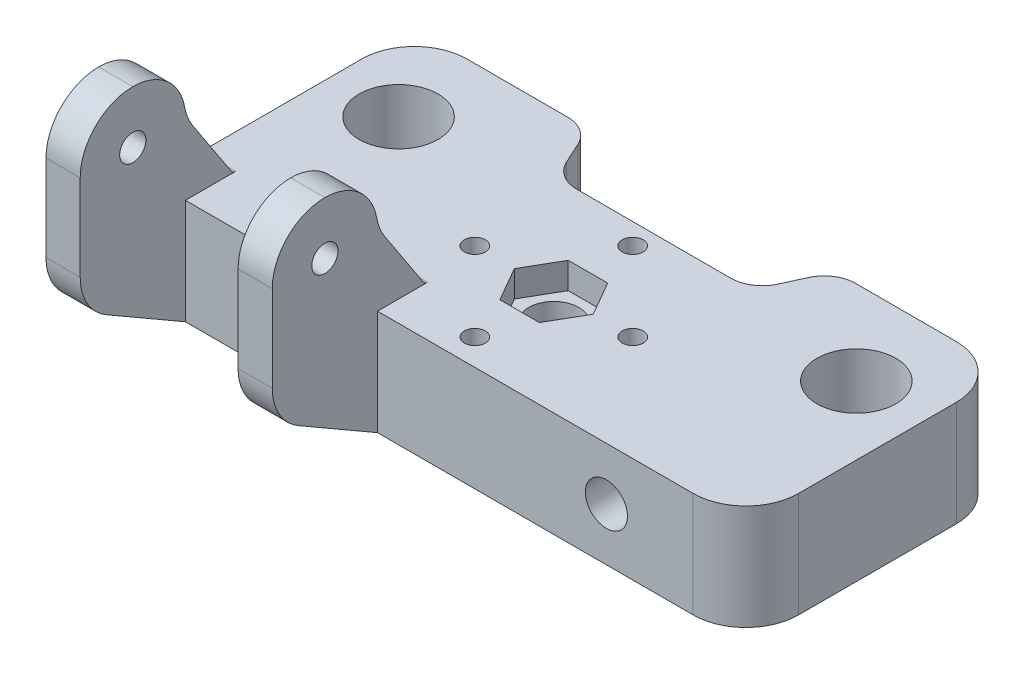
SolidWorks part; units mm, degrees
material "ABS PC"
ref_plane "Front Plane" through (0, 0, 0) normal (0, 0, 1) x (1, 0, 0)
ref_plane "Top Plane" through (0, 0, 0) normal (0, 1, 0) x (1, 0, 0)
ref_plane "Right Plane" through (0, 0, 0) normal (1, 0, 0) x (0, 0, -1)
sketch "Sketch1" plane through (0, 0, 0) normal (0, 1, 0) x (1, 0, 0)
  line L0 (56.5, 0) -> (-56.5, 0)
  line L1 (56.5, 0) -> (56.5, 50)
  line L2 (-56.5, 0) -> (-56.5, 50)
  line L3 (56.5, 50) -> (-56.5, 50)
  dimension "D1" = 113
  dimension "D2" = 50
extrude "Boss-Extrude1" add sketch "Sketch1" along normal blind 20
sketch "Sketch2" plane through (0, 20, 0) normal (0, 1, 0) x (1, 0, 0)
  line L1 (56.5, 0) -> (56.5, 50) construction
  line L3 (56.5, 50) -> (-56.5, 50) construction
  circle A0 centre (-43.5, 34) radius 7.5
  circle A1 centre (43.5, 34) radius 7.5
  circle A2 centre (0, 20) radius 4.75
  circle A3 centre (15, 20) radius 2
  circle A4 centre (-15, 20) radius 2
  circle A5 centre (0, 35) radius 2
  circle A6 centre (0, 5) radius 2
  dimension "D2" = 56.5
  dimension "D3" = 30
  dimension "D5" = 15
  dimension "D6" = 15
  dimension "D1" = 43.5
  dimension "D4" = 43.5
  dimension "D7" = 14
  dimension "D8" = 9.5
  dimension "D9" = 15
  dimension "D10" = 15
  dimension "D11" = 4
  dimension "D12" = 15
  dimension "D13" = 15
extrude "Cut-Extrude1" cut sketch "Sketch2" against normal through all
sketch "Sketch3" plane through (0, 20, 0) normal (0, 1, 0) x (1, 0, 0)
  line L1 (-3.75, 13.5048) -> (3.75, 13.5048)
  line L2 (3.75, 13.5048) -> (7.5, 20)
  line L3 (7.5, 20) -> (3.75, 26.4952)
  line L4 (3.75, 26.4952) -> (-3.75, 26.4952)
  line L5 (-3.75, 26.4952) -> (-7.5, 20)
  line L6 (-7.5, 20) -> (-3.75, 13.5048)
  circle A0 centre (0, 20) radius 6.4952 construction
  circle A1 centre (0, 20) radius 4.75 construction
  dimension "D1" = 15
extrude "Cut-Extrude2" cut sketch "Sketch3" against normal blind 5
sketch "Sketch5" plane through (0, 0, -50) normal (0, 0, -1) x (-1, 0, 0)
  line L3 (-56.5, 20) -> (-56.5, 0) construction
  line L4 (-56.5, 0) -> (56.5, 0) construction
  circle A0 centre (30, 10) radius 4
  circle A1 centre (-30, 10) radius 4
  dimension "D1" = 8
  dimension "D2" = 60
  dimension "D3" = 26.5
  dimension "D4" = 10
extrude "Cut-Extrude4" cut sketch "Sketch5" against normal through all
sketch "Sketch12" plane through (0, 20, 0) normal (0, 1, 0) x (1, 0, 0)
  line L4 (23.5, 50) -> (18.5, 39)
  line L5 (56.5, 50) -> (-56.5, 50) construction
  line L6 (18.5, 39) -> (-18.5, 39)
  line L7 (-18.5, 39) -> (-23.5, 50)
  line L8 (-23.5, 50) -> (23.5, 50)
  dimension "D2" = 11
  dimension "D3" = 33
  dimension "D4" = 33
  dimension "D5" = 5
  dimension "D6" = 5
extrude "Cut-Extrude6" cut sketch "Sketch12" against normal through all
fillet "Fillet5" radius 6 4 edges at (-23.5, 10, -50) (23.5, 10, -50) (-18.5, 10, -39) (18.5, 10, -39)
sketch "Sketch13" plane through (0, 0, 0) normal (0, 0, 1) x (1, 0, 0)
  line L0 (-50, 0) -> (-50, 43.7)
  line L1 (-50, 0) -> (-56.5, 0)
  line L2 (-50, 43.7) -> (-56.5, 43.7)
  line L3 (-56.5, 0) -> (-56.5, 43.7)
  line L4 (-56.5, 0) -> (56.5, 0) construction
  line L5 (-20, 0) -> (-13.5, 0)
  line L6 (-20, 0) -> (-20, 43.7)
  line L7 (-13.5, 0) -> (-13.5, 43.7)
  line L8 (-20, 43.7) -> (-13.5, 43.7)
  line L9 (-56.5, 20) -> (-56.5, 0) construction
  dimension "D3" = 30
  dimension "D1" = 43.7
  dimension "D2" = 6.5
extrude "Boss-Extrude2" add sketch "Sketch13" along normal blind 20
hole_wizard "Ø5.0 (5) Diameter Hole1" positions "Sketch15" profile "Sketch14" hole size "Ø5.0" standard "ANSI Metric" end condition through all
sketch "Sketch15" plane through (-13.5, 0, 0) normal (1, 0, 0) x (0, 0, -1)
  line L0 (0, 20) -> (0, 43.7) construction
  point P0 (-10, 33.7)
  dimension "D1" = 10
  dimension "D2" = 13.7
sketch "Sketch14" plane through (-13.5, 33.7, 10) normal (0, 1, 0) x (0, 0, -1)
  line L0 (0, 0) -> (0, 43)
  line L1 (0, 43) -> (2.5, 43)
  line L2 (2.5, 43) -> (2.5, 0)
  line L5 (2.5, 0) -> (0, 0)
  line L11 (0, -6.35) -> (0, 107.95) construction
  dimension "Thru Hole Dia." = 5
  dimension "Thru Hole Depth" = 43
sketch "Sketch16" plane through (-13.5, 0, 0) normal (1, 0, 0) x (0, 0, -1)
  line L0 (0, 0) -> (-20, 0)
  line L1 (-20, 0) -> (-20, 11.547)
  line L2 (-20, 0) -> (-20, 43.7) construction
  line L3 (-20, 11.547) -> (0, 0)
  dimension "D1" = 30
extrude "Cut-Extrude7" cut sketch "Sketch16" against normal through all
fillet "Fillet6" radius 10 2 edges at (-53.25, 11.547, 20) (-16.75, 11.547, 20)
fillet "Fillet7" radius 10 4 edges at (-16.75, 43.7, 0) (-16.75, 43.7, 20) (-53.25, 43.7, 20) (-53.25, 43.7, 0)
sketch "Sketch18" plane through (-56.5, 0, 0) normal (-1, 0, 0) x (0, 0, 1)
  line L0 (0, 33.7) -> (0, 20)
  line L1 (0, 20) -> (-9, 20)
  line L2 (-9, 20) -> (0, 33.7)
  dimension "D1" = 9
extrude "Boss-Extrude3" add sketch "Sketch18" against normal blind 6.5
fillet "Fillet8" radius 10 1 edges at (-53.25, 33.7, 0)
sketch "Sketch19" plane through (-13.5, 0, 0) normal (1, 0, 0) x (0, 0, -1)
  line L0 (0, 33.7) -> (0, 20)
  line L1 (0, 20) -> (9, 20)
  line L2 (9, 20) -> (0, 33.7)
  dimension "D1" = 9
extrude "Boss-Extrude4" add sketch "Sketch19" against normal blind 6.5
fillet "Fillet9" radius 10 1 edges at (-16.75, 33.7, 0)
fillet "Fillet10" radius 1 2 edges at (-16.75, 20, -9) (-53.25, 20, -9)
fillet "Fillet11" radius 10 3 edges at (-56.5, 10, -50) (56.5, 10, -50) (56.5, 10, 0)
